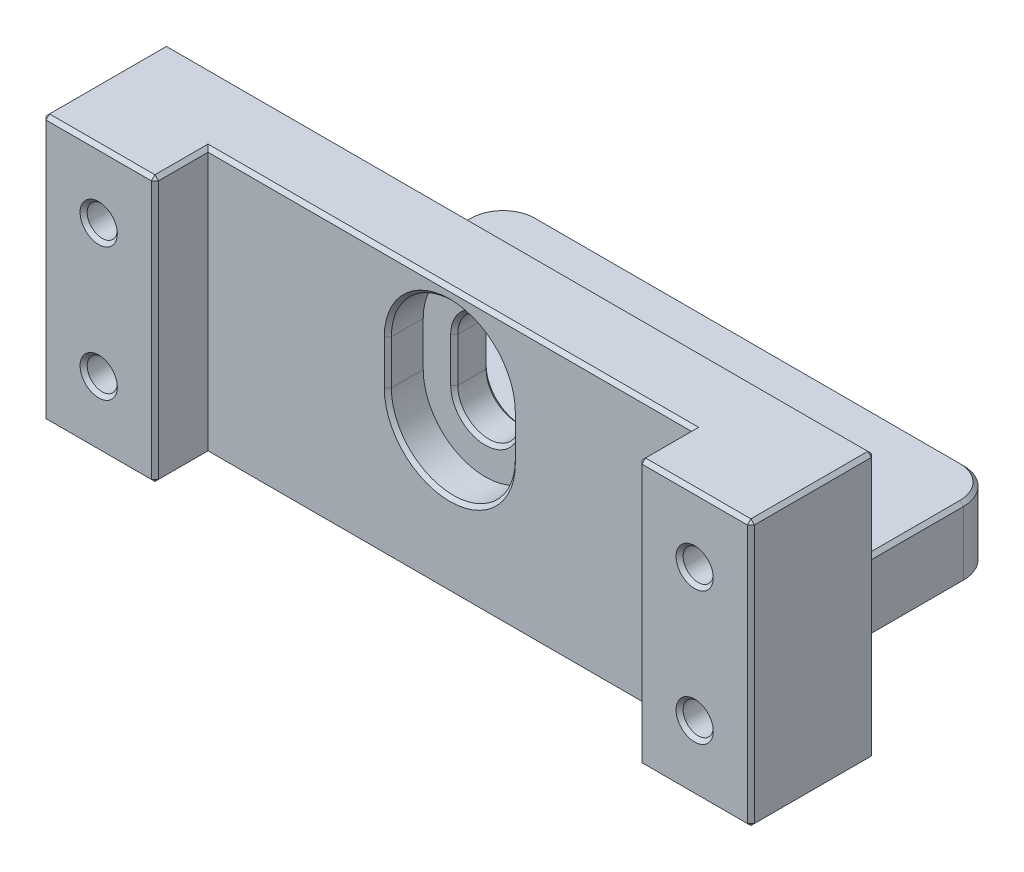
SolidWorks part; units mm, degrees
ref_plane "Front" through (0, 0, 0) normal (0, 0, 1) x (1, 0, 0)
ref_plane "Top" through (0, 0, 0) normal (0, 1, 0) x (1, 0, 0)
ref_plane "Right" through (0, 0, 0) normal (1, 0, 0) x (0, 0, -1)
ref_axis "Z AXIS" through (0, 0, 10.1914) along (0, 0, -1)
ref_axis "Y AXIS" through (0, 16.6631, 0) along (0, -1, 0)
ref_axis "X AXIS" through (18.31, 0, 0) along (-1, 0, 0)
sketch "Sketch1" plane through (0, 0, 0) normal (0, 1, 0) x (1, 0, 0)
  line L0 (-27.3, 0) -> (-27.3, 6)
  line L1 (-27.3, 6) -> (27.3, 6)
  line L2 (27.3, 6) -> (27.3, 0)
  line L3 (27.3, 0) -> (40, 0)
  line L4 (40, 0) -> (40, 14)
  line L5 (40, 14) -> (-40, 14)
  line L6 (-40, 14) -> (-40, 0)
  line L7 (-40, 0) -> (-27.3, 0)
  line L8 (-27.3, 0) -> (27.3, 0)
  line L9 (0, 0) -> (0, 6)
  point P10 (0, 0)
  dimension "D1" = 6
  dimension "D2" = 8
  dimension "D3" = 80
  dimension "D4" = 54.6
extrude "Boss-Extrude1" add sketch "Sketch1" along normal blind 30 contours L6 L7 L0 L1 L2 L3 L4 L5 region at (0, 0, -8.6537)
sketch "Sketch2" plane through (0, 0, 0) normal (0, -1, 0) x (1, 0, 0)
  line L1 (-40, -14) -> (40, -14)
  line L2 (-40, -14) -> (-40, -40)
  line L3 (-40, -40) -> (40, -40)
  line L4 (40, -14) -> (40, -40)
  point P4 (40, -14)
  dimension "D1" = 26
extrude "Boss-Extrude2" add sketch "Sketch2" against normal blind 8 contours L2 L1 L4 L3
hole_wizard "CBORE for M3 Hex Socket Head Cap Screw1" positions "Sketch3" profile "Sketch4" counterbore size "M3" standard "ISO"
sketch "Sketch3" plane through (0, 0, 0) normal (0, -1, 0) x (-1, 0, 0)
  line L0 (0, 40) -> (0, 14) construction
  line L1 (40, 40) -> (-40, 40) construction
  line L3 (40, 14) -> (-40, 14) construction
  line L4 (40, 14) -> (-40, 14) construction
  point P14 (-22.5, 26.5)
  point P17 (22.5, 26.5)
  dimension "D1" = 45
  dimension "D2" = 12.5
sketch "Sketch4" plane through (-22.5, 0, -26.5) normal (1, 0, 0) x (0, 0, -1)
  line L0 (0, 0) -> (0, 21.0215)
  line L1 (0, 21.0215) -> (1.7, 20)
  line L2 (1.7, 20) -> (1.7, 3.4)
  line L3 (1.7, 3.4) -> (3.25, 3.4)
  line L5 (3.25, 3.4) -> (3.25, 0.025)
  line L6 (3.25, 0.025) -> (3.275, 0)
  line L7 (3.275, 0) -> (0, 0)
  line L8 (-3.25, 0.025) -> (-3.275, 0) construction
  line L10 (0, 21.0215) -> (-1.7, 20) construction
  line L11 (0, -6.35) -> (0, 107.95) construction
  dimension "Hole Dia." = 3.4
  dimension "Hole Depth" = 20
  dimension "C'Bore Dia." = 6.5
  dimension "C'Bore Depth" = 3.4
  dimension "Near C'Sink Dia." = 6.55
  dimension "Near C'Sink Angle" = 90
  dimension "Drill Angle" = 118
sketch "Sketch5" plane through (0, 0, 0) normal (0, -1, 0) x (1, 0, 0)
  line L0 (-40, -14) -> (40, -14) construction
  line L1 (-40, -40) -> (-28, -40)
  line L2 (-40, -40) -> (-40, -14)
  line L3 (-40, -14) -> (-28, -14)
  line L4 (-28, -40) -> (-28, -14)
  line L5 (-40, -14) -> (40, -14) construction
  line L6 (0, -14) -> (0, -40) construction
  line L7 (-40, -40) -> (40, -40) construction
  line L8 (40, -14) -> (28, -14)
  line L9 (28, -40) -> (28, -14)
  line L10 (40, -40) -> (28, -40)
  line L11 (40, -40) -> (40, -14)
  dimension "D1" = 12
extrude "Cut-Extrude1" cut sketch "Sketch5" against normal blind 8 contours L8 L9 L10 L11 | L2 L1 L4 L3
fillet "Fillet1" radius 4 2 edges at (28, 4, -40) (-28, 4, -40)
hole_wizard "CBORE for M3 Hex Socket Head Cap Screw2" positions "Sketch6" profile "Sketch7" counterbore size "M3" standard "ISO"
sketch "Sketch6" plane through (0, 0, -14) normal (0, 0, -1) x (-1, 0, 0)
  line L0 (27.3, 30) -> (27.3, 0) construction
  line L1 (-27.3, 30) -> (-27.3, 0) construction
  line L2 (27.3, 30) -> (27.3, 0) construction
  line L3 (-27.3, 30) -> (-27.3, 0) construction
  line L4 (27.3, 15) -> (40, 15) construction
  line L5 (40, 30) -> (40, 0) construction
  line L7 (33.65, 15) -> (33.65, 0) construction
  line L8 (40, 0) -> (28, 0) construction
  line L9 (0, 30) -> (0, 0) construction
  line L10 (-40, 30) -> (40, 30) construction
  point P17 (33.65, 7.5)
  point P20 (33.65, 22.5)
  point P29 (0, 0)
  point P30 (-33.65, 7.5)
  point P31 (-33.65, 22.5)
sketch "Sketch7" plane through (33.65, 22.5, -14) normal (1, 0, 0) x (0, 1, 0)
  line L0 (0, 0) -> (0, 21.0215)
  line L1 (0, 21.0215) -> (1.7, 20)
  line L2 (1.7, 20) -> (1.7, 4.4)
  line L3 (1.7, 4.4) -> (3.25, 4.4)
  line L5 (3.25, 4.4) -> (3.25, 0.025)
  line L6 (3.25, 0.025) -> (3.275, 0)
  line L7 (3.275, 0) -> (0, 0)
  line L8 (-3.25, 0.025) -> (-3.275, 0) construction
  line L10 (0, 21.0215) -> (-1.7, 20) construction
  line L11 (0, -6.35) -> (0, 107.95) construction
  dimension "Hole Dia." = 3.4
  dimension "Hole Depth" = 20
  dimension "C'Bore Dia." = 6.5
  dimension "C'Bore Depth" = 4.4
  dimension "Near C'Sink Dia." = 6.55
  dimension "Near C'Sink Angle" = 90
  dimension "Drill Angle" = 118
hole_wizard "CBORE SLOT for M6 Hex Socket Head Cap Screw2" positions "Sketch14" profile "Sketch15" size "M6" standard "ISO" slot yes end condition through all
sketch "Sketch14" plane through (0, 0, -6) normal (0, 0, 1) x (1, 0, 0)
  line L0 (-28, 8) -> (28, 8) construction
  line L1 (-28, 8) -> (28, 8) construction
  line L5 (0, 0) -> (0, 30) construction
  line L6 (-27.3, 0) -> (27.3, 0) construction
  line L7 (-27.3, 30) -> (27.3, 30) construction
  line L9 (0, 13) -> (0, 25) construction
  point P9 (0, 19)
  point P30 (0, 30)
  point P31 (0.3349, 13.4294)
  point P32 (0, 22.7485)
  dimension "D1" = 12
  dimension "D2" = 11
sketch "Sketch15" plane through (0, 19, -6) normal (1, 0, 0) x (0, -1, 0)
  line L0 (0, 0) -> (0, 34)
  line L1 (0, 34) -> (3.5, 34)
  line L3 (3.5, 34) -> (3.5, 4)
  line L4 (3.5, 4) -> (7, 4)
  line L5 (7, 4) -> (7, 0)
  line L7 (7, 0) -> (0, 0)
  line L11 (0, -6.35) -> (0, 107.95) construction
  dimension "Thru Hole Dia." = 7
  dimension "Thru Hole Depth" = 34
  dimension "C'Bore Dia." = 14
  dimension "C'Bore Depth" = 4
chamfer "Chamfer1" distance 0.4 angle 45 51 edges at (31.95, 22.5, 0) (31.95, 7.5, 0) (-28, 8, -25) (-26.8284, 8, -38.8284) (28, 8, -25) (0, 8, -40) (26.8284, 8, -38.8284) (-34, 0, -14) (-33.65, 0, 0) (-27.3, 0, -3) (0, 0, -6) (27.3, 0, -3) (-28, 0, -25) (-26.8284, 0, -38.8284) (0, 0, -40) (26.8284, 0, -38.8284) (28, 0, -25) (34, 0, -14) (27.3, 15, 0) (33.65, 0, 0) (40, 15, 0) (40, 0, -7) (40, 15, -14) (0, 30, -14) (40, 30, -7) (33.65, 30, 0) (27.3, 30, -3) (0, 30, -6) (-27.3, 30, -3) (-40, 30, -7) (-40, 15, -14) (-40, 0, -7) (-40, 15, 0) (-33.65, 30, 0) (-27.3, 15, 0) (-35.35, 7.5, 0) (-35.35, 22.5, 0) (-22.5, 8, -24.8) (22.5, 8, -24.8) (0, 25, -14) (-3.5, 19, -14) (3.5, 19, -14) (0, 13, -14) (0, 25, -10) (-3.5, 19, -10) (3.5, 19, -10) (0, 13, -10) (0, 28.5, -6) (-7, 19, -6) (7, 19, -6) (0, 9.5, -6)
